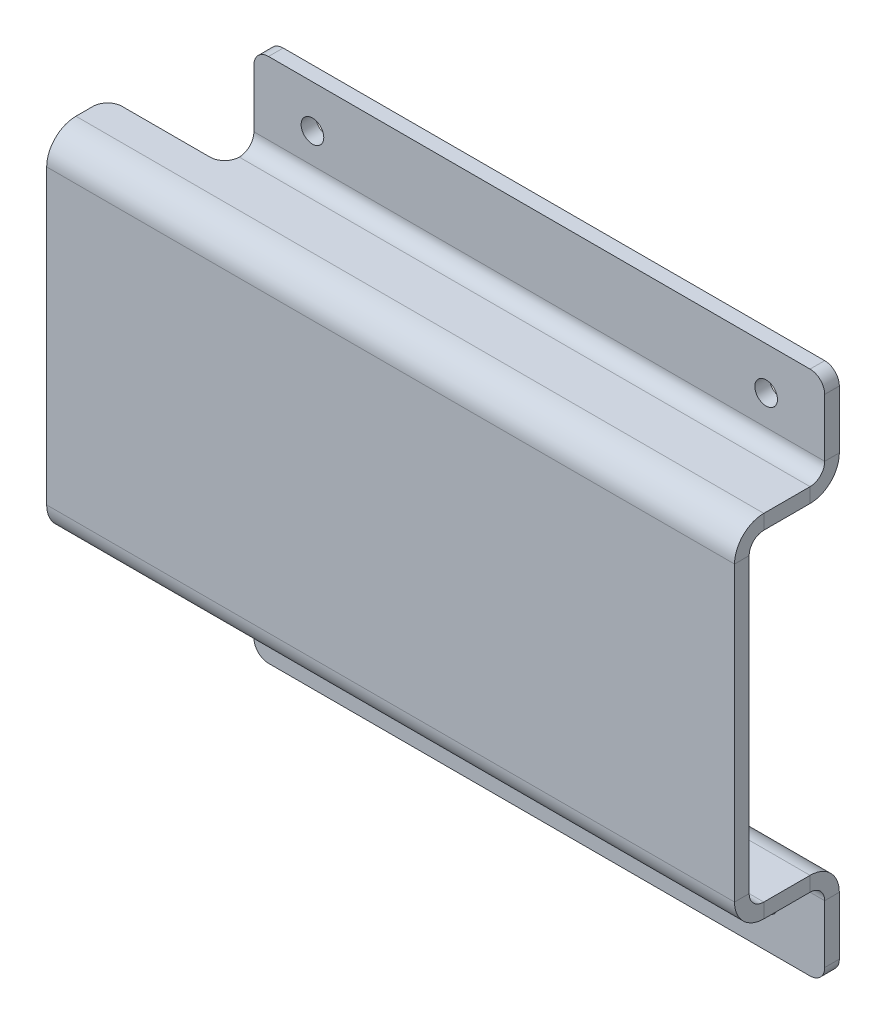
SolidWorks part; units mm, degrees
note: The reader was unsure of these and kept them because the rebuilt part matched: thickness of "Base-Flange1", "Edge-Flange1", "Edge-Flange2", "Sheet-Metal1", "Sheet-Metal2", "Sheet-Metal3", "Sheet-Metal4", "Sheet-Metal5", "Sheet-Metal6", "Sheet-Metal7"; flange length of "Edge-Flange1", "Edge-Flange2".
material "Plain Carbon Steel"
ref_plane "Front Plane" through (0, 0, 0) normal (0, 0, 1) x (1, 0, 0)
ref_plane "Top Plane" through (0, 0, 0) normal (0, 1, 0) x (1, 0, 0)
ref_plane "Right Plane" through (0, 0, 0) normal (1, 0, 0) x (0, 0, -1)
sketch "Sketch1" plane through (0, 0, 0) normal (0, 0, 1) x (1, 0, 0)
  line L1 (74.6125, 38.1) -> (-74.6125, 38.1)
  line L2 (74.6125, 38.1) -> (74.6125, -38.1)
  line L3 (74.6125, -38.1) -> (-74.6125, -38.1)
  line L4 (-74.6125, 38.1) -> (-74.6125, -38.1)
  line L5 (74.6125, 38.1) -> (-74.6125, -38.1) construction
  line L6 (74.6125, -38.1) -> (-74.6125, 38.1) construction
  point P0 (0, 0)
  dimension "D1" = 149.225
  dimension "D2" = 76.2
base flange "Base-Flange1" sketch "Sketch1" thickness 3.175 reverse thickness direction no parameters "D1"=3.175
edge flange "Edge-Flange1" sketch "Sketch8" flange profiles "Sketch8", "Sketch10" flange angle 90 flange length 22.733 flange position material inside bend radius 3.175 thickness 3.175 relief rectangular parameters "D1"=2.54, "D6"=10, "D8"=0.254
sketch "Sketch8" plane through (0, -38.1, -3.175) normal (0, 1, 0) x (1, 0, 0)
  line L2 (-74.6125, 0) -> (-74.6125, 19.558)
  line L3 (-74.6125, 19.558) -> (74.6125, 19.558)
  line L4 (74.6125, 19.558) -> (74.6125, 0)
  line L5 (74.6125, 0) -> (-74.6125, 0) construction
  line L6 (74.6125, 0) -> (-74.6125, 0)
sketch "Sketch10" plane through (0, 38.1, -3.175) normal (0, -1, 0) x (-1, 0, 0)
  line L0 (74.6125, 0) -> (-74.6125, 0) construction
  line L1 (74.6125, 0) -> (-74.6125, 0)
  line L2 (74.6125, 0) -> (74.6125, 19.558)
  line L3 (74.6125, 19.558) -> (-74.6125, 19.558)
  line L4 (-74.6125, 19.558) -> (-74.6125, 0)
bend "EdgeBend1" bend radius 3.175 bend angle 90 parameters "D5"=1
bend "EdgeBend2" bend radius 3.175 bend angle 90 parameters "D5"=3
sketch "Sketch17" plane through (0, -38.1, 0) normal (0, -1, 0) x (1, 0, 0)
  line L1 (-74.6125, -22.733) -> (-49.2125, -22.733)
  line L2 (-74.6125, -22.733) -> (-74.6125, -13.208)
  line L3 (-74.6125, -13.208) -> (-49.2125, -13.208)
  line L4 (-49.2125, -22.733) -> (-49.2125, -13.208)
  dimension "D1" = 9.525
  dimension "D2" = 25.4
extrude "Cut-Extrude1" cut sketch "Sketch17" against normal through all normal cut yes
edge flange "Edge-Flange2" sketch "Sketch15" flange profiles "Sketch15", "Sketch16" flange angle 90 flange length 22.0878 flange position material inside bend radius 3.175 thickness 3.175 relief rectangular parameters "D1"=2.54, "D6"=10, "D8"=0.254
sketch "Sketch15" plane through (0, -38.1, -22.733) normal (0, 0, 1) x (-1, 0, 0)
  line L2 (-74.6125, 0) -> (-74.6125, 18.9128)
  line L3 (-74.6125, 18.9128) -> (49.2125, 18.9128)
  line L4 (49.2125, 18.9128) -> (49.2125, 0)
  line L13 (49.2125, 0) -> (-74.6125, 0) construction
  line L14 (49.2125, 0) -> (-74.6125, 0)
sketch "Sketch16" plane through (0, 38.1, -22.733) normal (0, 0, 1) x (1, 0, 0)
  line L0 (74.6125, 0) -> (-49.2125, 0) construction
  line L1 (74.6125, 0) -> (-49.2125, 0)
  line L2 (74.6125, 0) -> (74.6125, 18.9128)
  line L3 (74.6125, 18.9128) -> (-49.2125, 18.9128)
  line L4 (-49.2125, 18.9128) -> (-49.2125, 0)
bend "EdgeBend3" bend radius 3.175 bend angle 90 parameters "D5"=4
bend "EdgeBend4" bend radius 3.175 bend angle 90 parameters "D5"=5
sketch "Sketch18" plane through (0, 0, -22.733) normal (0, 0, -1) x (-1, 0, 0)
  line L0 (49.2125, -57.0128) -> (-74.6125, -57.0128) construction
  line L1 (-74.6125, -57.0128) -> (-74.6125, -41.275) construction
  circle A0 centre (-61.9125, -47.4878) radius 2.3876
  dimension "D1" = 9.525
  dimension "D3" = 4.7752
  dimension "D2" = 12.7
extrude "Cut-Extrude2" cut sketch "Sketch18" against normal through all normal cut yes
pattern_linear "LPattern1" count 2 spacing 98.425 along (-1, 0, 0) count 2 spacing 95.25 along (0, 1, 0) of "Cut-Extrude2"
fillet "Fillet1" radius 3.175 8 edges at (-49.2125, -36.5125, -13.208) (-49.2125, 36.5125, -13.208) (-74.6125, -36.5125, -13.208) (-74.6125, 36.5125, -13.208) (-49.2125, 57.0128, -21.1455) (74.6125, 57.0128, -21.1455) (74.6125, -57.0128, -21.1455) (-49.2125, -57.0128, -21.1455)
sketch "Sketch19" plane through (0, 0, -19.558) normal (0, 0, 1) x (1, 0, 0)
  point P0 (-36.5125, 47.7622)
  point P1 (-36.5125, -47.4878)
  point P3 (61.9125, -47.4878)
  point P5 (61.9125, 47.7622)
hole_wizard "#10 (0.1935) Diameter Hole1" positions "Sketch20" profile "Sketch21" hole size "#10" standard "ANSI Inch" end condition up to next
sketch "Sketch20" plane through (0, 0, -19.558) normal (0, 0, 1) x (1, 0, 0)
  point P0 (-36.5125, 47.7622)
  point P3 (61.9125, 47.7622)
  point P6 (61.9125, -47.4878)
  point P9 (-36.5125, -47.4878)
sketch "Sketch21" plane through (-36.5125, 47.7622, -19.558) normal (1, 0, 0) x (0, -1, 0)
  line L0 (0, 0) -> (0, 3.175)
  line L1 (0, 3.175) -> (2.4574, 3.175)
  line L2 (2.4574, 3.175) -> (2.4574, 0)
  line L5 (2.4574, 0) -> (0, 0)
  line L11 (0, -6.35) -> (0, 107.95) construction
  dimension "Thru Hole Dia." = 4.9149
  dimension "Thru Hole Depth" = 3.175
sketch "Bend-Lines1" [suppressed] plane through (0, 0, 0) normal (0, 1, 0) x (1, 0, 0)
sketch "Bounding-Box1" [suppressed] plane through (0, 0, 0) normal (0, 1, 0) x (1, 0, 0)
sheet metal parameters "Sheet-Metal1" thickness 3.175 parameters "D1"=2.54, "D7"=3.0378
flat pattern "Flat-Pattern1" [suppressed]
sketch "Bend-Lines2" plane through (0, 0, 0) normal (0, 1, 0) x (1, 0, 0)
sketch3d "Bounding-Box2" [suppressed]
  line L0 (50.8, -38.1, 0) -> (-50.8, -38.1, 0) construction
  line L1 (50.8, 38.1, 0) -> (-50.8, 38.1, 0) construction
  line L2 (50.8, -38.1, 0) -> (50.8, 38.1, 0) construction
  line L3 (-50.8, -38.1, 0) -> (-50.8, 38.1, 0) construction
sheet metal parameters "Sheet-Metal2" thickness 3.175 parameters "D1"=2.54, "D7"=3.0378
flat pattern "Flat-Pattern1"
sketch "Bend-Lines2" plane through (0, 0, 0) normal (0, 0, 1) x (1, 0, 0)
  line L0 (-50.8, -35.71) -> (50.8, -35.71) construction
  line L1 (-50.8, -35.71) -> (50.8, -35.71) construction
  line L2 (50.8, 35.71) -> (-50.8, 35.71) construction
  line L3 (50.8, 35.71) -> (-50.8, 35.71) construction
sketch3d "Bounding-Box2" [suppressed]
  line L0 (50.8, 56.0531, 0) -> (50.8, -56.0531, 0) construction
  line L1 (-50.8, 56.0531, 0) -> (-50.8, -56.0531, 0) construction
  line L2 (50.8, 56.0531, 0) -> (-50.8, 56.0531, 0) construction
  line L3 (50.8, -56.0531, 0) -> (-50.8, -56.0531, 0) construction
bend of the flat pattern "Flatten-<EdgeBend1>1"
bend of the flat pattern "Flatten-<EdgeBend2>1"
sheet metal parameters "Sheet-Metal3" thickness 3.175 parameters "D1"=2.54, "D7"=3.0378
flat pattern "Flat-Pattern1"
sketch "Bend-Lines2" plane through (0, 0, 0) normal (0, 0, 1) x (1, 0, 0)
  line L0 (-50.8, -35.71) -> (50.8, -35.71) construction
  line L1 (-50.8, -35.71) -> (50.8, -35.71) construction
  line L2 (50.8, 35.71) -> (-50.8, 35.71) construction
  line L3 (50.8, 35.71) -> (-50.8, 35.71) construction
  line L4 (50.8, 53.6631) -> (-25.4, 53.6631) construction
  line L5 (-25.4, -53.6631) -> (50.8, -53.6631) construction
  line L6 (50.8, 53.6631) -> (-25.4, 53.6631) construction
  line L7 (-25.4, -53.6631) -> (50.8, -53.6631) construction
sketch3d "Bounding-Box2" [suppressed]
  line L0 (50.7998, -70.3231, 0) -> (50.8, 70.3231, 0) construction
  line L1 (-50.8, -70.323, 0) -> (-50.7999, 70.3232, 0) construction
  line L2 (50.7998, -70.3231, 0) -> (-50.8, -70.323, 0) construction
  line L3 (50.8, 70.3231, 0) -> (-50.7999, 70.3232, 0) construction
bend of the flat pattern "Flatten-<EdgeBend1>1"
bend of the flat pattern "Flatten-<EdgeBend2>1"
bend of the flat pattern "Flatten-<EdgeBend3>1"
bend of the flat pattern "Flatten-<EdgeBend4>1"
sheet metal parameters "Sheet-Metal4" thickness 3.175 parameters "D1"=2.54, "D7"=3.0378
flat pattern "Flat-Pattern1"
sketch "Bend-Lines2" plane through (0, 0, 0) normal (0, 0, 1) x (1, 0, 0)
  line L0 (-50.8, -35.71) -> (50.8, -35.71) construction
  line L1 (-50.8, -35.71) -> (50.8, -35.71) construction
  line L2 (50.8, 35.71) -> (-50.8, 35.71) construction
  line L3 (50.8, 35.71) -> (-50.8, 35.71) construction
sketch3d "Bounding-Box2" [suppressed]
  line L0 (50.7999, -56.0531, 0) -> (50.8, 56.0531, 0) construction
  line L1 (-50.8, -56.0529, 0) -> (-50.7999, 56.0532, 0) construction
  line L2 (50.7999, -56.0531, 0) -> (-50.8, -56.0529, 0) construction
  line L3 (50.8, 56.0531, 0) -> (-50.7999, 56.0532, 0) construction
bend of the flat pattern "Flatten-<EdgeBend1>1"
bend of the flat pattern "Flatten-<EdgeBend2>1"
sheet metal parameters "Sheet-Metal5" thickness 3.175 parameters "D1"=2.54, "D7"=3.0378
flat pattern "Flat-Pattern1"
sketch "Bend-Lines2" plane through (0, 0, 0) normal (0, 0, 1) x (1, 0, 0)
  line L0 (-50.8, -35.71) -> (50.8, -35.71) construction
  line L1 (-50.8, -35.71) -> (50.8, -35.71) construction
  line L2 (50.8, 35.71) -> (-50.8, 35.71) construction
  line L3 (50.8, 35.71) -> (-50.8, 35.71) construction
  line L4 (50.8, 53.6631) -> (-25.4, 53.6631) construction
  line L5 (-25.4, -53.6631) -> (50.8, -53.6631) construction
  line L6 (50.8, 53.6631) -> (-25.4, 53.6631) construction
  line L7 (-25.4, -53.6631) -> (50.8, -53.6631) construction
sketch3d "Bounding-Box2" [suppressed]
  line L0 (50.7998, -70.3231, 0) -> (50.8, 70.3231, 0) construction
  line L1 (-50.8, -70.323, 0) -> (-50.7999, 70.3232, 0) construction
  line L2 (50.7998, -70.3231, 0) -> (-50.8, -70.323, 0) construction
  line L3 (50.8, 70.3231, 0) -> (-50.7999, 70.3232, 0) construction
bend of the flat pattern "Flatten-<EdgeBend1>1"
bend of the flat pattern "Flatten-<EdgeBend2>1"
bend of the flat pattern "Flatten-<EdgeBend3>1"
bend of the flat pattern "Flatten-<EdgeBend4>1"
sheet metal parameters "Sheet-Metal6" thickness 3.175 parameters "D1"=2.54, "D7"=3.0378
flat pattern "Flat-Pattern1" [suppressed]
sketch "Bend-Lines2" plane through (0, 0, 0) normal (0, 0, 1) x (1, 0, 0)
  line L0 (-74.6125, -35.71) -> (74.6125, -35.71) construction
  line L1 (-74.6125, -35.71) -> (74.6125, -35.71) construction
  line L2 (74.6125, 35.71) -> (-74.6125, 35.71) construction
  line L3 (74.6125, 35.71) -> (-74.6125, 35.71) construction
  line L4 (74.6125, 53.6631) -> (-49.2125, 53.6631) construction
  line L5 (-49.2125, -53.6631) -> (74.6125, -53.6631) construction
  line L6 (74.6125, 53.6631) -> (-49.2125, 53.6631) construction
  line L7 (-49.2125, -53.6631) -> (74.6125, -53.6631) construction
sketch3d "Bounding-Box2" [suppressed]
  line L0 (-74.6123, 73.3611, 0) -> (74.6125, 73.3609, 0) construction
  line L1 (-74.6125, -73.3608, 0) -> (74.6123, -73.361, 0) construction
  line L2 (-74.6123, 73.3611, 0) -> (-74.6125, -73.3608, 0) construction
  line L3 (74.6125, 73.3609, 0) -> (74.6123, -73.361, 0) construction
bend of the flat pattern "Flatten-<EdgeBend1>1"
bend of the flat pattern "Flatten-<EdgeBend2>1"
bend of the flat pattern "Flatten-<EdgeBend3>1"
bend of the flat pattern "Flatten-<EdgeBend4>1"
sketch "Sketch19-2" [suppressed] plane through (0, 16.211, 0) normal (0, 0, 1) x (1, 0, 0)
  point P0 (-36.5125, 47.625)
  point P1 (-36.5125, -47.625)
  point P3 (61.9125, -47.625)
  point P5 (61.9125, 47.625)
sheet metal parameters "Sheet-Metal7" thickness 3.175 parameters "D1"=2.54, "D7"=3.0378
flat pattern "Flat-Pattern1" [suppressed]
sketch "Bend-Lines2" plane through (0, 0, 0) normal (0, 0, 1) x (1, 0, 0)
  line L0 (-74.6125, -35.4905) -> (74.6125, -35.4905) construction
  line L1 (-74.6125, -35.4905) -> (74.6125, -35.4905) construction
  line L2 (74.6125, 35.4905) -> (-74.6125, 35.4905) construction
  line L3 (74.6125, 35.4905) -> (-74.6125, 35.4905) construction
  line L4 (74.6125, 53.0044) -> (-49.2125, 53.0044) construction
  line L5 (-49.2125, -53.0044) -> (74.6125, -53.0044) construction
  line L6 (74.6125, 53.0044) -> (-49.2125, 53.0044) construction
  line L7 (-49.2125, -53.0044) -> (74.6125, -53.0044) construction
sketch3d "Bounding-Box2" [suppressed]
  line L0 (-74.6124, 72.4829, 0) -> (74.6125, 72.4827, 0) construction
  line L1 (-74.6125, -72.4825, 0) -> (74.6123, -72.4827, 0) construction
  line L2 (-74.6124, 72.4829, 0) -> (-74.6125, -72.4825, 0) construction
  line L3 (74.6125, 72.4827, 0) -> (74.6123, -72.4827, 0) construction
bend of the flat pattern "Flatten-<EdgeBend1>1"
bend of the flat pattern "Flatten-<EdgeBend2>1"
bend of the flat pattern "Flatten-<EdgeBend3>1"
bend of the flat pattern "Flatten-<EdgeBend4>1"
sketch "Sketch19-1" [suppressed] plane through (0, 15.4698, 0) normal (0, 0, 1) x (1, 0, 0)
  point P0 (-36.5125, 47.7622)
  point P1 (-36.5125, -47.4878)
  point P3 (61.9125, -47.4878)
  point P5 (61.9125, 47.7622)
